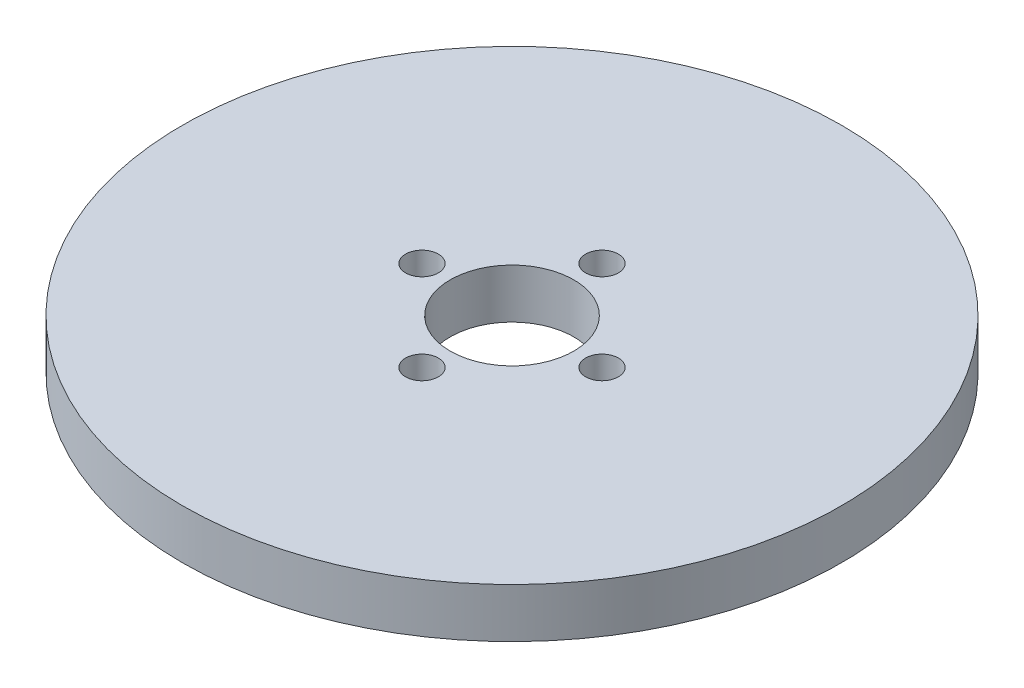
SolidWorks part; units mm, degrees
ref_plane "Front Plane" through (0, 0, 0) normal (0, 0, 1) x (1, 0, 0)
ref_plane "Top Plane" through (0, 0, 0) normal (0, 1, 0) x (1, 0, 0)
ref_plane "Right Plane" through (0, 0, 0) normal (1, 0, 0) x (0, 0, -1)
sketch "Sketch1" plane through (0, 0, 0) normal (0, 1, 0) x (1, 0, 0)
  circle A0 centre (0, 0) radius 40
  dimension "FLANGE_OD" = 80
extrude "Boss-Extrude1" add sketch "Sketch1" along normal blind 6
sketch "Sketch2" plane through (0, 0, 0) normal (0, 1, 0) x (1, 0, 0)
  circle A0 centre (0, 0) radius 7.5
  dimension "BORE_D" = 15
extrude "Cut-Extrude1" cut sketch "Sketch2" along normal through all
sketch "Sketch3" plane through (0, 6, 0) normal (0, 1, 0) x (1, 0, 0)
  circle A0 centre (0, 0) radius 10.9256 construction
  circle A1 centre (-10.9256, 0) radius 1.9859
  dimension "BOLT_D" = 3.9718
  dimension "BOLT_PCD" = 21.8512
extrude "Cut-Extrude2" cut sketch "Sketch3" against normal blind 4.9536
pattern_circular "CirPattern1" count 4 over 360 about axis through (0, 0, 0) along (0, 1, 0) of "Cut-Extrude2"
